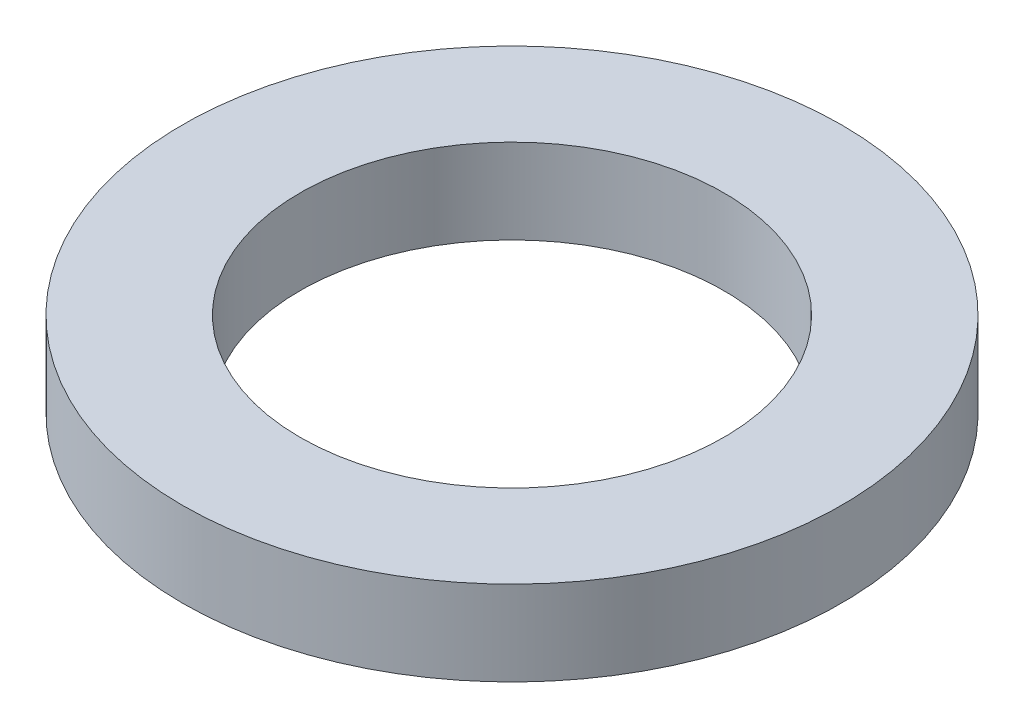
SolidWorks part; units mm, degrees
ref_plane "Front Plane" through (0, 0, 0) normal (0, 0, 1) x (1, 0, 0)
ref_plane "Top Plane" through (0, 0, 0) normal (0, 1, 0) x (1, 0, 0)
ref_plane "Right Plane" through (0, 0, 0) normal (1, 0, 0) x (0, 0, -1)
sketch "Sketch1" plane through (0, 0, 0) normal (0, 1, 0) x (1, 0, 0)
  circle A0 centre (0, 0) radius 70
  dimension "FLANGE_OD" = 140
extrude "Boss-Extrude1" add sketch "Sketch1" along normal blind 18
sketch "Sketch2" plane through (0, 0, 0) normal (0, 1, 0) x (1, 0, 0)
  circle A0 centre (0, 0) radius 45
  dimension "BORE_D" = 90
extrude "Cut-Extrude1" cut sketch "Sketch2" along normal through all
sketch "Sketch3" plane through (0, 18, 0) normal (0, 1, 0) x (1, 0, 0)
  circle A0 centre (0, 0) radius 30.9767 construction
  circle A1 centre (-30.9767, 0) radius 4.1856
  dimension "BOLT_D" = 8.3713
  dimension "BOLT_PCD" = 61.9535
extrude "Cut-Extrude2" cut sketch "Sketch3" against normal blind 16.6586 rebuild error yes
pattern_circular "CirPattern1" count 4 over 360 rebuild error yes
